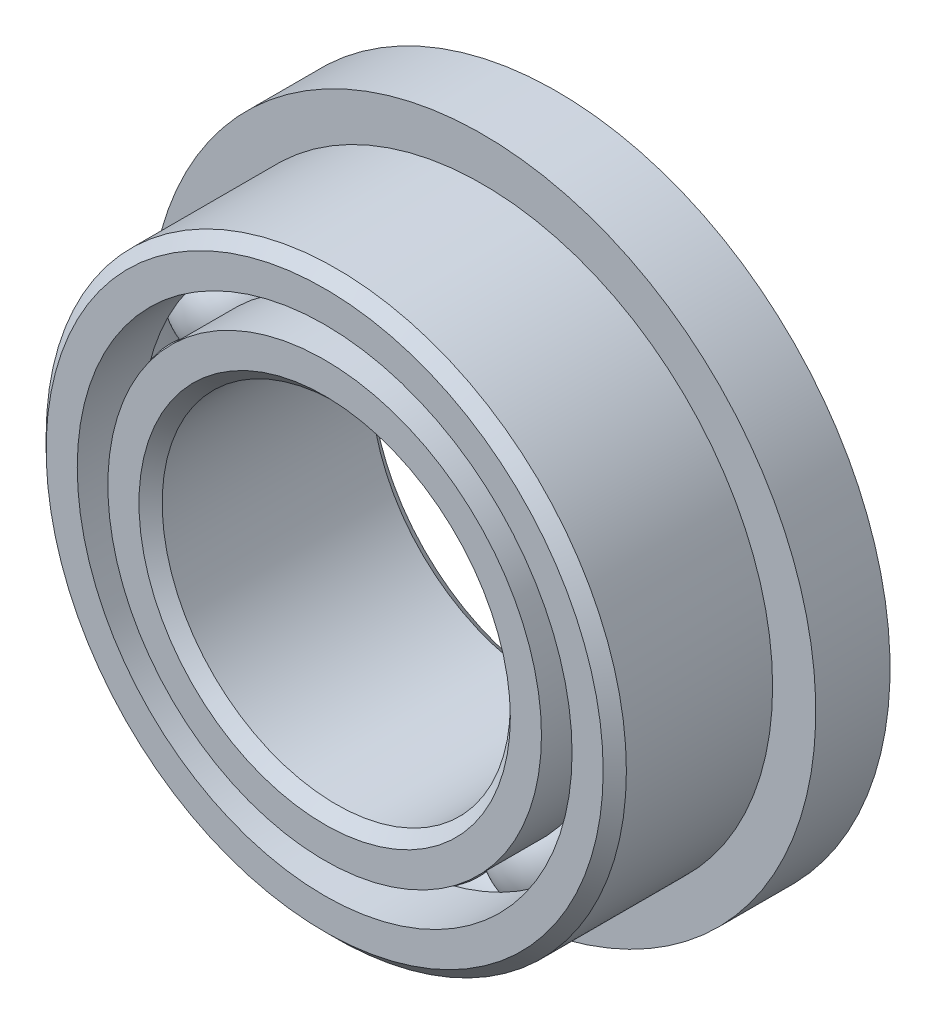
SolidWorks part; units mm, degrees
material "AISI 1020"
ref_plane "Front Plane" through (0, 0, 0) normal (0, 0, 1) x (1, 0, 0)
ref_plane "Top Plane" through (0, 0, 0) normal (0, 1, 0) x (1, 0, 0)
ref_plane "Right Plane" through (0, 0, 0) normal (1, 0, 0) x (0, 0, -1)
sketch "Sketch1" plane through (0, 0, 0) normal (1, 0, 0) x (0, 0, -1)
  line L0 (-1.5875, 0) -> (1.5875, 0) construction
  line L1 (0, 3.9688) -> (0, -3.9688) construction
  line L2 (1.4288, 3.9687) -> (-1.4288, 3.9687)
  line L3 (-1.4288, 3.9687) -> (-1.5875, 3.81)
  line L4 (-1.5875, 3.81) -> (-1.5875, 3.3843)
  line L5 (-1.5875, 3.3843) -> (-0.7056, 3.3843)
  line L6 (1.5875, 3.3843) -> (0.7056, 3.3843)
  line L7 (1.5875, 3.81) -> (1.5875, 3.3843)
  line L8 (1.4288, 3.9687) -> (1.5875, 3.81)
  line L9 (0, 3.9688) -> (0, 3.175) construction
  line L10 (0, 3.175) -> (0, 2.3813) construction
  arc A0 (-0.7056, 3.3843) -> (0.7056, 3.3843) centre (0, 3.175) cw
  point P14 (0, 2.3813)
  dimension "D3" = 1.4111
  dimension "D1" = 45
  dimension "Width" = 3.175
  dimension "OD" = 7.9375
  dimension "D2" = 0.1588
  dimension "Shaft Dia" = 4.7625
  dimension "D4" = 0.2093
revolve "Revolve1" add sketch "Sketch1" angle 360 about L0
sketch "Sketch3" plane through (0, 0, 0) normal (1, 0, 0) x (0, 0, -1)
  line L0 (-1.4288, 3.9687) -> (-1.5875, 3.81) construction
  line L1 (-0.7056, 2.9657) -> (-1.5875, 2.9657)
  line L2 (-1.5875, 3.81) -> (-1.5875, 3.3843) construction
  line L3 (-1.5875, 2.9657) -> (-1.5875, 2.54)
  line L5 (-1.5875, 2.54) -> (-1.4288, 2.3812)
  line L6 (-1.4288, 2.3812) -> (1.4288, 2.3812)
  line L7 (1.5875, 3.81) -> (1.5875, 3.3843) construction
  line L8 (1.4288, 2.3812) -> (1.5875, 2.54)
  line L10 (1.5875, 2.54) -> (1.5875, 2.9657)
  line L11 (1.5875, 2.9657) -> (0.7056, 2.9657)
  line L13 (1.4288, 3.9687) -> (1.5875, 3.81) construction
  arc A1 (0.7056, 2.9657) -> (-0.7056, 2.9657) centre (0, 3.175) cw
  arc A2 (0.7056, 3.3843) -> (-0.7056, 3.3843) centre (0, 3.175) ccw construction
revolve "Revolve3" add sketch "Sketch3" angle 360 about L0
sketch "Sketch5" plane through (0, 0, 0) normal (1, 0, 0) x (0, 0, -1)
  line L0 (1.5875, 3.81) -> (1.5875, 3.3843) construction
  line L1 (1.5875, 3.5972) -> (0.5715, 3.5972)
  line L2 (1.5875, 3.5972) -> (1.5875, 4.5593)
  line L3 (1.5875, 4.5593) -> (0.5715, 4.5593)
  line L4 (0.5715, 3.5972) -> (0.5715, 4.5593)
  line L5 (1.5875, 0) -> (-1.5875, 0) construction
  dimension "Th" = 1.016
  dimension "Flange OD" = 9.1186
revolve "Revolve5" add sketch "Sketch5" angle 360 about L5
sketch "Sketch4" plane through (0, 0, 0) normal (1, 0, 0) x (0, 0, -1)
  line L0 (-0.736, 3.175) -> (0.736, 3.175)
  arc A2 (-0.736, 3.175) -> (0.736, 3.175) centre (0, 3.175) cw
  arc A3 (0.7056, 3.3843) -> (-0.7056, 3.3843) centre (0, 3.175) ccw construction
revolve "Revolve4" add sketch "Sketch4" angle 360 about L0
ref_axis "Axis1" through (0, 0, -1.5875) along (0, 0, 1)
pattern_circular "CirPattern1" count 12 every 30 about axis through (0, 0, -1.5875) along (0, 0, 1) of bodies 104
equation "\"D2@Sketch1\" = \"Width@Sketch1\"*.05"
equation "\"D3@Sketch1\" = \"Width@Sketch1\"/2.25"
equation "\"D4@Sketch1\" = (((\"OD@Sketch1\"-\"Width@Sketch1\")/2)/3.25)/3.5"
equation "\"D2@CirPattern1\" = 360/\"Balls@CirPattern1\""
